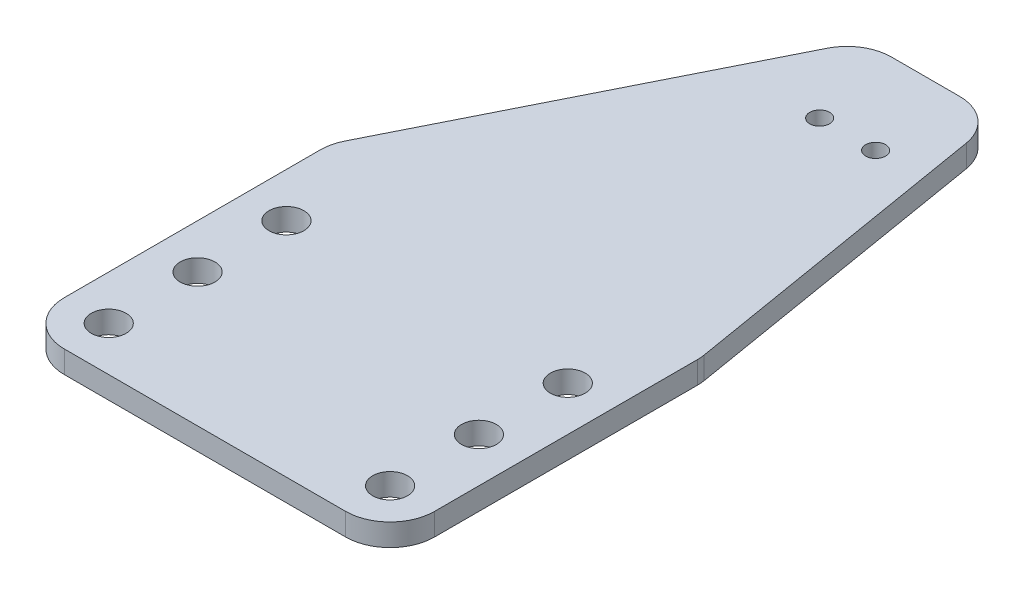
SolidWorks part; units mm, degrees
material "6061-T6 (SS)"
ref_plane "Front Plane" through (0, 0, 0) normal (0, 0, 1) x (1, 0, 0)
ref_plane "Top Plane" through (0, 0, 0) normal (0, 1, 0) x (1, 0, 0)
ref_plane "Right Plane" through (0, 0, 0) normal (1, 0, 0) x (0, 0, -1)
sketch "Sketch1" plane through (0, 0, 0) normal (0, 1, 0) x (1, 0, 0)
  line L0 (0, 0) -> (52.9167, 0)
  line L1 (52.9167, 0) -> (52.9167, 44.45)
  line L3 (44.45, 95.25) -> (25.4, 95.25)
  line L5 (0, 44.45) -> (52.9167, 44.45) construction
  line L6 (19.0551, 82.5602) -> (28.1397, 82.5602) construction
  line L7 (0, 44.45) -> (0, 0)
  line L8 (0, 44.45) -> (25.4, 95.25)
  line L9 (44.45, 95.25) -> (52.9167, 44.45)
  circle A0 centre (6.35, 6.35) radius 2.4892
  circle A1 centre (6.35, 19.05) radius 2.4892
  circle A2 centre (6.35, 31.75) radius 2.4892
  circle A3 centre (46.5667, 6.35) radius 2.4892
  circle A4 centre (46.5667, 19.05) radius 2.4892
  circle A5 centre (46.5667, 31.75) radius 2.4892
  circle A6 centre (31.7551, 82.5602) radius 1.4224
  circle A7 centre (39.7551, 82.5602) radius 1.4224
  point P7 (20.643, 82.5602)
  point P26 (25.5543, 82.5602)
  point P27 (5.7202, 6.35)
  dimension "D9" = 4.9784
  dimension "D12" = 4.9784
  dimension "D17" = 2.8448
  dimension "D4" = 12.7
  dimension "D5" = 12.7
  dimension "D6" = 6.35
  dimension "D8" = 12.7
  dimension "D2" = 50.8
  dimension "D3" = 19.05
  dimension "D10" = 12.7
  dimension "D11" = 12.7
  dimension "D13" = 40.2167
  dimension "D14" = 6.35
  dimension "D15" = 38.1102
  dimension "D16" = 8
  dimension "D7" = 12.7
  dimension "D18" = 6.35
  dimension "D19" = 25.4
extrude "Boss-Extrude1" add sketch "Sketch1" along normal blind 3.175
fillet "Fillet1" radius 6.35 6 edges at (52.9167, 1.5875, 0) (0, 1.5875, -44.45) (44.45, 1.5875, -95.25) (52.9167, 1.5875, -44.45) (0, 1.5875, 0) (25.4, 1.5875, -95.25)
equation "\"D16@Sketch1\"=8mm"
